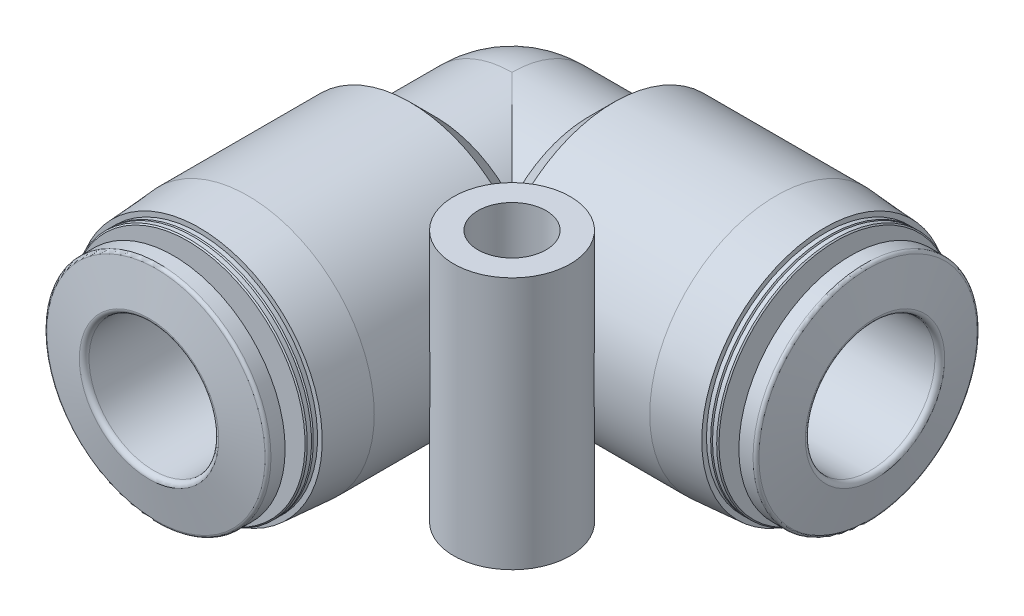
SolidWorks part; units mm, degrees
ref_plane "Ebene vorne" through (0, 0, 0) normal (0, 0, 1) x (1, 0, 0)
ref_plane "Ebene oben" through (0, 0, 0) normal (0, 1, 0) x (1, 0, 0)
ref_plane "Ebene rechts" through (0, 0, 0) normal (1, 0, 0) x (0, 0, -1)
sketch "Skizze1" plane through (0, 0, 0) normal (0, 0, 1) x (1, 0, 0)
  line L0 (0, 6.24) -> (4.74, 6.24)
  line L1 (4.74, 6.24) -> (6.3, 7.8)
  line L2 (6.3, 7.8) -> (16.3, 7.8)
  line L3 (16.3, 7.8) -> (19.3, 7.5902)
  line L4 (19.3, 7.5902) -> (19.3, 7.3)
  line L5 (19.3, 7.3) -> (19.5569, 7.3)
  line L6 (19.5569, 7.3) -> (19.6146, 7.2)
  line L7 (19.6146, 7.2) -> (19.6724, 7.3)
  line L8 (19.6724, 7.3) -> (19.9293, 7.3)
  line L9 (19.9293, 7.3) -> (20, 7.2293)
  line L10 (20, 7.2293) -> (20, 4.7)
  line L11 (20, 4.7) -> (20.525, 4.7)
  line L12 (20.9, 5.075) -> (20.9, 6.9)
  line L13 (20.9, 6.9) -> (21.7737, 6.9)
  line L14 (21.9707, 6.7347) -> (22.4, 4.3)
  line L15 (22.4, 4.3) -> (22.4, 0)
  line L16 (22.4, 0) -> (-6.24, 0)
  line L17 (22.4, 0) -> (-6.24, 0) construction
  arc A0 (-6.24, 0) -> (0, 6.24) centre (0, 0) cw
  arc A1 (20.525, 4.7) -> (20.9, 5.075) centre (20.525, 5.075) ccw
  arc A2 (21.7737, 6.9) -> (21.9707, 6.7347) centre (21.7737, 6.7) cw
revolve "Rotation1" add sketch "Skizze1" angle 360 about L17 reverse direction yes
sketch "Skizze2" plane through (0, 0, 0) normal (0, 1, 0) x (1, 0, 0)
  line L0 (0, 0) -> (6.24, 0)
  line L1 (6.24, 0) -> (6.24, -4.74)
  line L2 (6.24, -4.74) -> (7.8, -6.3)
  line L3 (7.8, -6.3) -> (7.8, -16.3)
  line L4 (7.8, -16.3) -> (7.5902, -19.3)
  line L5 (7.5902, -19.3) -> (7.3, -19.3)
  line L6 (7.3, -19.3) -> (7.3, -19.5569)
  line L7 (7.3, -19.5569) -> (7.2, -19.6146)
  line L8 (7.2, -19.6146) -> (7.3, -19.6724)
  line L9 (7.3, -19.6724) -> (7.3, -19.9293)
  line L10 (7.3, -19.9293) -> (7.2293, -20)
  line L11 (7.2293, -20) -> (4.7, -20)
  line L12 (4.7, -20) -> (4.7, -20.525)
  line L13 (5.075, -20.9) -> (6.9, -20.9)
  line L14 (6.9, -20.9) -> (6.9, -21.7737)
  line L15 (6.7347, -21.9707) -> (4.3, -22.4)
  line L16 (4.3, -22.4) -> (0, -22.4)
  line L17 (0, -22.4) -> (0, 0)
  line L18 (0, -22.4) -> (0, 0) construction
  arc A0 (4.7, -20.525) -> (5.075, -20.9) centre (5.075, -20.525) ccw
  arc A1 (6.9, -21.7737) -> (6.7347, -21.9707) centre (6.7, -21.7737) cw
revolve "Rotation2" add sketch "Skizze2" angle 360 about L18 reverse direction yes
sketch "Skizze3" plane through (0, 0, 0) normal (1, 0, 0) x (0, 0, -1)
  line L0 (4.68, 1) -> (4.68, -1)
  line L1 (4.68, -1) -> (7.7356, -1)
  line L2 (7.7356, 1) -> (4.68, 1)
  arc A0 (7.7356, -1) -> (7.7356, 1) centre (0, 0) ccw
extrude "Aufsatz-Linear austragen1" add sketch "Skizze3" along normal blind 6.3
sketch "Skizze4" plane through (0, 0, 0) normal (0, 0, 1) x (1, 0, 0)
  line L0 (-7.7356, -1) -> (-4.68, -1)
  line L1 (-4.68, -1) -> (-4.68, 1)
  line L2 (-4.68, 1) -> (-7.7356, 1)
  arc A0 (-7.7356, 1) -> (-7.7356, -1) centre (0, 0) ccw
extrude "Aufsatz-Linear austragen2" add sketch "Skizze4" along normal blind 6.3
sketch "Skizze5" plane through (0, 0, 0) normal (0, 0, 1) x (1, 0, 0)
  line L0 (-7.7356, -1) -> (-4.68, -1)
  line L1 (-4.68, -1) -> (-4.68, 1)
  line L2 (-4.68, 1) -> (-7.7356, 1)
  line L3 (0, 1) -> (0, -1) construction
  arc A0 (-7.7356, 1) -> (-7.7356, -1) centre (0, 0) ccw
revolve "Rotation3" add sketch "Skizze5" angle 90 about L3
sketch "Skizze6" plane through (0, 0, 0) normal (0, 1, 0) x (1, 0, 0)
  line L0 (0, -12) -> (12, -12)
  line L1 (12, -12) -> (12, 0)
  line L2 (12, 0) -> (0, 0)
  line L3 (0, 0) -> (0, -12)
extrude "Aufsatz-Linear austragen3" add sketch "Skizze6" against normal blind 1 and the other way blind 1
ref_plane "Ebene1" through (0, 0, 10) normal (0, 0, 1) x (1, 0, 0)
sketch "Skizze7" plane through (0, 0, 10) normal (0, 0, 1) x (1, 0, 0)
  line L0 (10, 7.8) -> (13.6, 7.8)
  line L1 (13.6, 7.8) -> (13.6, -7.8)
  line L2 (13.6, -7.8) -> (10, -7.8)
  line L3 (10, -7.8) -> (10, 7.8)
  line L4 (10, -7.8) -> (10, 7.8) construction
revolve "Rotation4" add sketch "Skizze7" angle 360 about L4
hole_wizard "Bohrung1" positions "Skizze9" profile "Skizze8" legacy
sketch "Skizze9" plane through (0, -7.8, 0) normal (0, -1, 0) x (-1, 0, 0)
  point P0 (-10, -10)
sketch "Skizze8" plane through (10, -7.8, 10) normal (1, 0, 0) x (0, 0, -1)
  line L0 (0, 0) -> (0, 15.6)
  line L1 (0, 15.6) -> (2.1, 15.6)
  line L2 (2.1, 15.6) -> (2.1, 0)
  line L3 (2.1, 0) -> (0, 0)
  line L4 (0, 110) -> (0, -10) construction
  dimension "Durchmesser" = 4.2
  dimension "Tiefe" = 15.6
sketch "Skizze10" plane through (0, 0, 0) normal (0, 0, 1) x (1, 0, 0)
  line L0 (0, 2.3) -> (4.3, 2.3)
  line L1 (4.3, 2.3) -> (4.3, 3.8)
  line L2 (4.5, 4) -> (22.1, 4)
  line L3 (22.4, 4.3) -> (22.4, 0)
  line L4 (22.4, 0) -> (-2.3, 0)
  line L5 (22.4, 0) -> (-2.3, 0) construction
  arc A0 (-2.3, 0) -> (0, 2.3) centre (0, 0) cw
  arc A1 (4.3, 3.8) -> (4.5, 4) centre (4.5, 3.8) cw
  arc A2 (22.1, 4) -> (22.4, 4.3) centre (22.1, 4.3) ccw
revolve "Schnitt-Rotation1" cut sketch "Skizze10" angle 360 about L5
sketch "Skizze11" plane through (0, 0, 0) normal (0, 1, 0) x (1, 0, 0)
  line L0 (0, 0) -> (2.3, 0)
  line L1 (2.3, 0) -> (2.3, -4.3)
  line L2 (2.3, -4.3) -> (3.8, -4.3)
  line L3 (4, -4.5) -> (4, -22.1)
  line L4 (4.3, -22.4) -> (0, -22.4)
  line L5 (0, -22.4) -> (0, 0)
  line L6 (0, -22.4) -> (0, 0) construction
  arc A0 (3.8, -4.3) -> (4, -4.5) centre (3.8, -4.5) cw
  arc A1 (4, -22.1) -> (4.3, -22.4) centre (4.3, -22.1) ccw
revolve "Schnitt-Rotation2" cut sketch "Skizze11" angle 360 about L6
